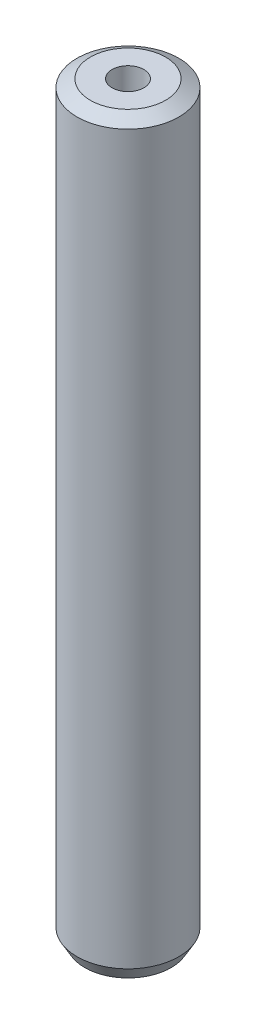
SolidWorks part; units mm, degrees
ref_plane "Front Plane" through (0, 0, 0) normal (0, 0, 1) x (1, 0, 0)
ref_plane "Top Plane" through (0, 0, 0) normal (0, 1, 0) x (1, 0, 0)
ref_plane "Right Plane" through (0, 0, 0) normal (1, 0, 0) x (0, 0, -1)
sketch "Sketch1" plane through (0, 0, 0) normal (0, 1, 0) x (1, 0, 0)
  circle A0 centre (0, 0) radius 20
  dimension "SHAFT_OD" = 40
extrude "Boss-Extrude1" add sketch "Sketch1" along normal blind 293.748
sketch "Sketch2" plane through (0, 0, 0) normal (0, 1, 0) x (1, 0, 0)
  circle A0 centre (0, 0) radius 6.2403
  dimension "BORE_D" = 12.4807
extrude "Cut-Extrude1" cut sketch "Sketch2" along normal through all
chamfer "Chamfer1" distance 3.036 angle 60 2 edges at (0, 293.748, 20) (0, 0, 20) first distance on face at (0, 293.748, 20) first distance on face at (0, 0, 6.2403)
